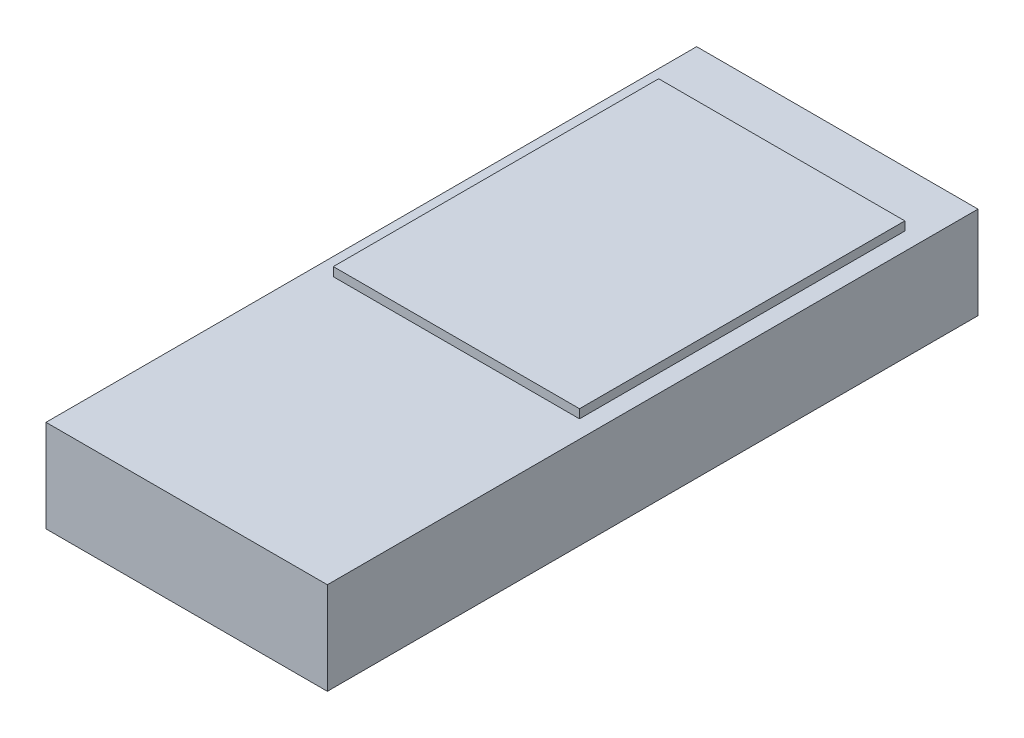
SolidWorks part; units mm, degrees
ref_plane "Front Plane" through (0, 0, 0) normal (0, 0, 1) x (1, 0, 0)
ref_plane "Top Plane" through (0, 0, 0) normal (0, 1, 0) x (1, 0, 0)
ref_plane "Right Plane" through (0, 0, 0) normal (1, 0, 0) x (0, 0, -1)
sketch "Sketch2" plane through (0, 0, 0) normal (0, 1, 0) x (1, 0, 0)
  line L0 (0, 0) -> (0, -93.98) construction
  line L2 (-40.64, -187.96) -> (40.64, -187.96)
  line L3 (-40.64, -187.96) -> (-40.64, 0)
  line L4 (-40.64, 0) -> (40.64, 0)
  line L5 (40.64, -187.96) -> (40.64, 0)
  line L6 (-40.64, -187.96) -> (40.64, 0) construction
  line L7 (-40.64, 0) -> (40.64, -187.96) construction
  dimension "D1" = 81.28
  dimension "D2" = 187.96
extrude "Boss-Extrude1" add sketch "Sketch2" along normal blind 26.67
sketch "Sketch4" plane through (0, 26.67, 0) normal (0, 1, 0) x (1, 0, 0)
  line L0 (0, -187.96) -> (0, -111.76) construction
  line L1 (-40.64, -187.96) -> (40.64, -187.96) construction
  line L2 (0, -111.76) -> (0, -63.0451) construction
  line L4 (-35.56, -16.0551) -> (35.56, -16.0551)
  line L5 (-35.56, -16.0551) -> (-35.56, -110.0351)
  line L6 (-35.56, -110.0351) -> (35.56, -110.0351)
  line L7 (35.56, -16.0551) -> (35.56, -110.0351)
  line L8 (-35.56, -16.0551) -> (35.56, -110.0351) construction
  line L9 (-35.56, -110.0351) -> (35.56, -16.0551) construction
extrude "Boss-Extrude2" add sketch "Sketch4" along normal blind 2.54
ref_point "Point1"
ref_axis "Axis1" through (0, 0, 187.96) along (0, 0, -1)
sketch "Sketch5" plane through (-40.64, 0, 0) normal (-1, 0, 0) x (0, 0, 1)
  line L0 (63.0451, 29.21) -> (187.96, 29.21) construction
